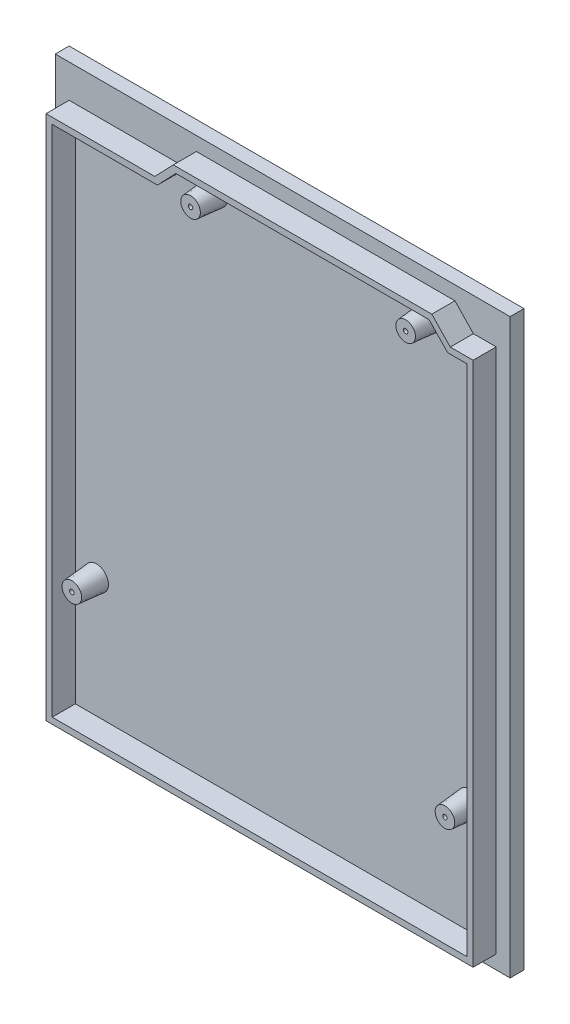
SolidWorks part; units mm, degrees
ref_plane "Front Plane" through (0, 0, 0) normal (1, 0, 0) x (0, 1, 0)
ref_plane "Top Plane" through (0, 0, 0) normal (0, 0, 1) x (0, 1, 0)
ref_plane "Right Plane" through (0, 0, 0) normal (0, 1, 0) x (-1, 0, 0)
sketch "Sketch1" plane through (0, 0, 0) normal (0, 0, 1) x (0, 1, 0)
  line L9 (43.1099, 53.4526) -> (-31.1901, 53.4526)
  line L10 (-31.1901, 53.4526) -> (-31.1901, -5.5474)
  line L11 (-31.1901, -5.5474) -> (43.1099, -5.5474)
  line L13 (43.1099, 53.4526) -> (43.1099, -5.5474)
  point P0 (42.7278, -5.5474)
extrude "Boss-Extrude1" add sketch "Sketch1" along normal blind 1.8
sketch "Sketch5" plane through (0, 0, 0) normal (0, 0, 1) x (0, 1, 0)
  line L0 (-28.5901, 50.8526) -> (-28.5901, -2.9474)
  line L1 (-28.5901, -2.9474) -> (38.0099, -2.9474)
  line L2 (38.0099, -2.9474) -> (38.0099, -0.4432)
  line L3 (38.0099, -0.4432) -> (40.5099, 1.9529)
  line L4 (40.5099, 1.9529) -> (40.5099, 34.8056)
  line L5 (40.5099, 34.8056) -> (38.0099, 37.2017)
  line L6 (38.0099, 37.2017) -> (38.0099, 50.8526)
  line L8 (38.0099, 50.8526) -> (-28.5901, 50.8526)
  line L19 (43.1099, 53.4526) -> (-31.1901, 53.4526) construction
  line L24 (-31.1901, 53.4526) -> (-31.1901, -5.5474) construction
  line L34 (43.1099, -5.5474) -> (43.1099, 53.4526) construction
  line L35 (-31.1901, -5.5474) -> (43.1099, -5.5474) construction
  point P19 (40.5099, 18.3793)
  dimension "D1" = 2.5
  dimension "D2" = 2.6
  dimension "D3" = 2.5
  dimension "D4" = 2.6
  dimension "D5" = 2.6
  dimension "D6" = 2.6
extrude "Extrude-Thin1" add sketch "Sketch5" along normal blind 3 from surface thin starting at face at (-23.9526, 5.9599, 1.8) thin type one direction wall 0.8
sketch "Sketch7" plane through (0, 0, 1.8) normal (0, 0, 1) x (1, 0, 0)
  line L1 (2.9474, 38.0099) -> (0.4432, 38.0099) construction
  line L2 (-34.8056, 40.5099) -> (-1.9529, 40.5099) construction
  line L3 (2.9474, 38.0099) -> (2.9474, -28.5901) construction
  line L4 (-50.8526, 38.0099) -> (-50.8526, -28.5901) construction
  line L5 (-50.8526, 38.0099) -> (-37.2017, 38.0099) construction
  circle A0 centre (-4.8026, 37.9099) radius 1.55
  circle A1 centre (-32.7026, 37.9099) radius 1.55
  circle A2 centre (0.2974, -14.1401) radius 1.55
  circle A3 centre (-48.1026, -13.0401) radius 1.55
  dimension "D1" = 3.1
  dimension "D6" = 2.75
  dimension "D2" = 2.6
  dimension "D3" = 7.75
  dimension "D4" = 0
  dimension "D5" = 27.9
  dimension "D7" = 2.65
  dimension "D8" = 52.15
  dimension "D9" = 51.05
extrude "Extrude-Thin2" add sketch "Sketch7" along normal blind 3.2 draft 5 thin thin type one direction reverse wall 1.54
